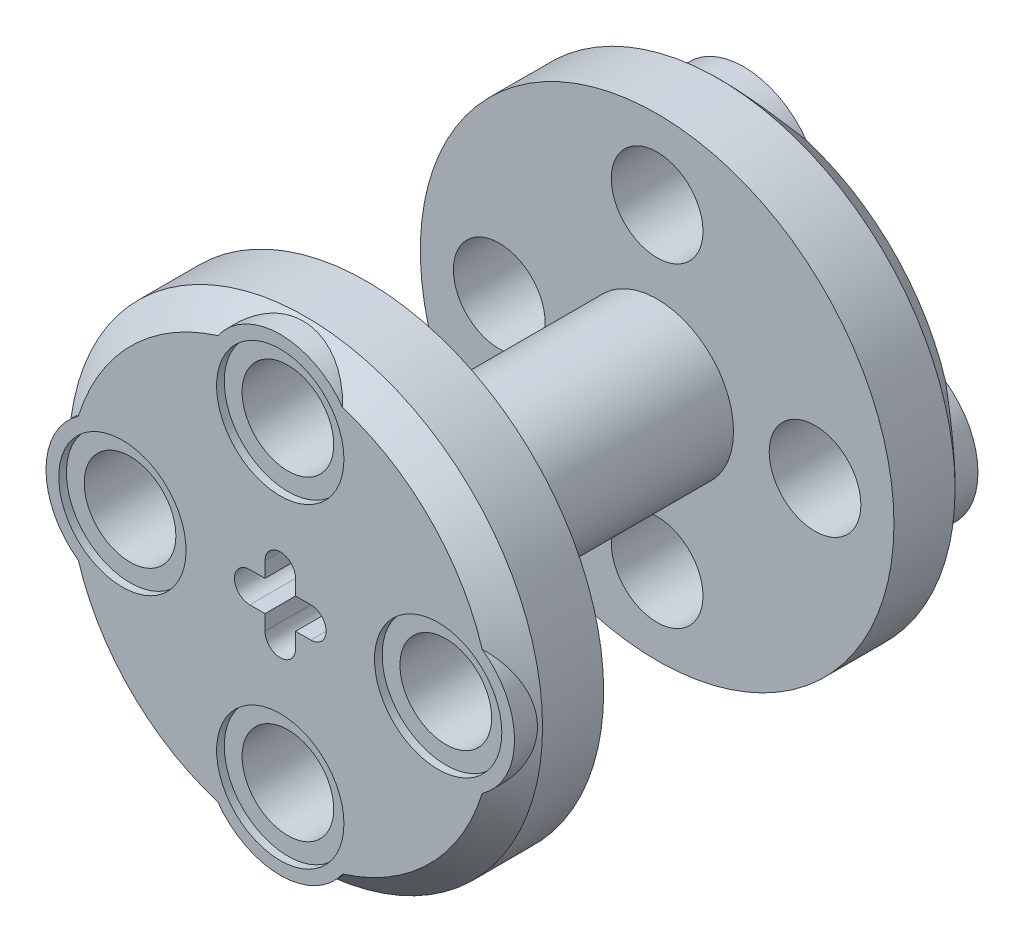
SolidWorks part; units mm, degrees
material "PVC Rigid"
ref_plane "Front Plane" through (0, 0, 0) normal (0, 0, 1) x (1, 0, 0)
ref_plane "Top Plane" through (0, 0, 0) normal (0, 1, 0) x (1, 0, 0)
ref_plane "Right Plane" through (0, 0, 0) normal (1, 0, 0) x (0, 0, -1)
sketch "Sketch1" plane through (0, 0, 0) normal (0, 0, 1) x (1, 0, 0)
  line L0 (0, 7.874) -> (0, -7.874) construction
  line L1 (-7.874, 0) -> (0, 7.874) construction
  line L2 (-7.874, 0) -> (0, -7.874) construction
  line L3 (0, -7.874) -> (7.874, 0) construction
  line L4 (0, 7.874) -> (7.874, 0) construction
  line L5 (0, 0) -> (0, 9.7901) construction
  circle A0 centre (0, 0) radius 11.811
  circle A1 centre (0, 7.874) radius 2.286
  circle A2 centre (7.874, 0) radius 2.286
  circle A3 centre (0, -7.874) radius 2.286
  circle A4 centre (-7.874, 0) radius 2.286
  dimension "D1" = 23.622
  dimension "D3" = 4.572
  dimension "D2" = 7.874
extrude "Extrude1" add sketch "Sketch1" along normal blind 4.318
chamfer "Chamfer1" distance 1.27 angle 45 1 edges at (11.811, 0, 4.318)
sketch "Sketch2" plane through (0, 0, 4.318) normal (0, 0, 1) x (1, 0, 0)
  circle A0 centre (0, 7.874) radius 2.794
  circle A1 centre (-7.874, 0) radius 2.794
  circle A2 centre (0, -7.874) radius 2.794
  circle A3 centre (7.874, 0) radius 2.794
  circle A4 centre (-7.874, 0) radius 2.286
  circle A5 centre (0, 7.874) radius 2.3067
  circle A6 centre (7.874, 0) radius 2.286
  circle A7 centre (0, -7.874) radius 2.2909
  dimension "D1" = 5.588
extrude "Extrude2" add sketch "Sketch2" against normal blind 4.318
ref_plane "Plane1" through (0, 0, -7.239) normal (0, 0, 1) x (1, 0, 0)
sketch "Sketch3" plane through (0, 0, 0) normal (0, 0, -1) x (-1, 0, 0)
  circle A0 centre (0, 0) radius 3.81
  dimension "D1" = 7.62
extrude "Extrude3" add sketch "Sketch3" along normal up to surface (7.239 mm away) up to plane "Plane1"
sketch "Sketch4" plane through (0, 0, 4.318) normal (0, 0, 1) x (1, 0, 0)
  line L0 (-1.524, 0) -> (1.524, 0) construction
  line L1 (-1.524, 0.762) -> (1.524, 0.762)
  line L2 (-1.524, -0.762) -> (1.524, -0.762)
  line L3 (0, 1.524) -> (0, -1.524) construction
  line L4 (0.762, 1.524) -> (0.762, -1.524)
  line L5 (-0.762, 1.524) -> (-0.762, -1.524)
  line L12 (0, -22.9897) -> (0, 22.9897) construction
  line L13 (38.7381, 0) -> (-38.7381, 0) construction
  arc A0 (-1.524, 0.762) -> (-1.524, -0.762) centre (-1.524, 0) ccw
  arc A1 (1.524, -0.762) -> (1.524, 0.762) centre (1.524, 0) ccw
  arc A2 (0.762, 1.524) -> (-0.762, 1.524) centre (0, 1.524) ccw
  arc A3 (-0.762, -1.524) -> (0.762, -1.524) centre (0, -1.524) ccw
  point P2 (0, 0)
  point P10 (0, 0)
  dimension "D1" = 1.524
  dimension "D2" = 3.048
  dimension "D3" = 1.524
extrude "Cut-Extrude1" cut sketch "Sketch4" against normal through all contours L1 A0 L2 L5 | L4 A2 L5 L1 | L2 A1 L1 L4 | L1 L5 L2 L4 | L5 A3 L4 L2 region at (-1.4529, 0, 4.318) region at (0, 1.4529, 4.318) region at (0, 0, 4.318) region at (1.4529, 0, 4.318) region at (0, -1.4529, 4.318)
mirror "Mirror1" about plane through (0, 0, -7.239) normal (0, 0, 1) of bodies 104
sketch "Sketch5" plane through (0, 0, 4.318) normal (0, 0, 1) x (1, 0, 0)
  circle A0 centre (0, 7.874) radius 3.175
  circle A1 centre (0, 7.874) radius 3.81
  circle A2 centre (0, 7.874) radius 2.286 construction
  circle A3 centre (0, 7.874) radius 2.286
  dimension "D1" = 6.35
  dimension "D2" = 7.62
extrude "Boss-Extrude3" add sketch "Sketch5" against normal up to surface (4.318 mm away) contours A1 | A3 up to face at (10.16, 0, 0)
sketch "Sketch6" plane through (0, 0, -18.796) normal (0, 0, -1) x (-1, 0, 0)
  circle A0 centre (0, 7.874) radius 2.286 construction
  circle A1 centre (0, 7.874) radius 3.175 construction
  circle A2 centre (0, 7.874) radius 3.81 construction
  circle A3 centre (0, 7.874) radius 2.286
  circle A4 centre (0, 7.874) radius 3.175
  circle A5 centre (0, 7.874) radius 3.81
extrude "Boss-Extrude5" add sketch "Sketch6" against normal up to surface (4.318 mm away) contours A5 | A3 up to face at (10.16, 0, -14.478)
extrude "Cut-Extrude2" cut sketch "Sketch5<3>" against normal blind 0.381 contours A0
sketch "Sketch5<3>" plane through (0, 0, 4.318) normal (0, 0, 1) x (1, 0, 0) same geometry as "Sketch5"
extrude "Cut-Extrude3" cut sketch "Sketch6<3>" against normal blind 0.381 contours A4
sketch "Sketch6<3>" plane through (0, 0, -18.796) normal (0, 0, -1) x (-1, 0, 0) same geometry as "Sketch6"
pattern_circular "CirPattern1" count 4 over 360 about axis through (0, 0, 4.318) along (0, 0, -1) of "Boss-Extrude3", "Cut-Extrude2", "Cut-Extrude3", "Boss-Extrude5"
